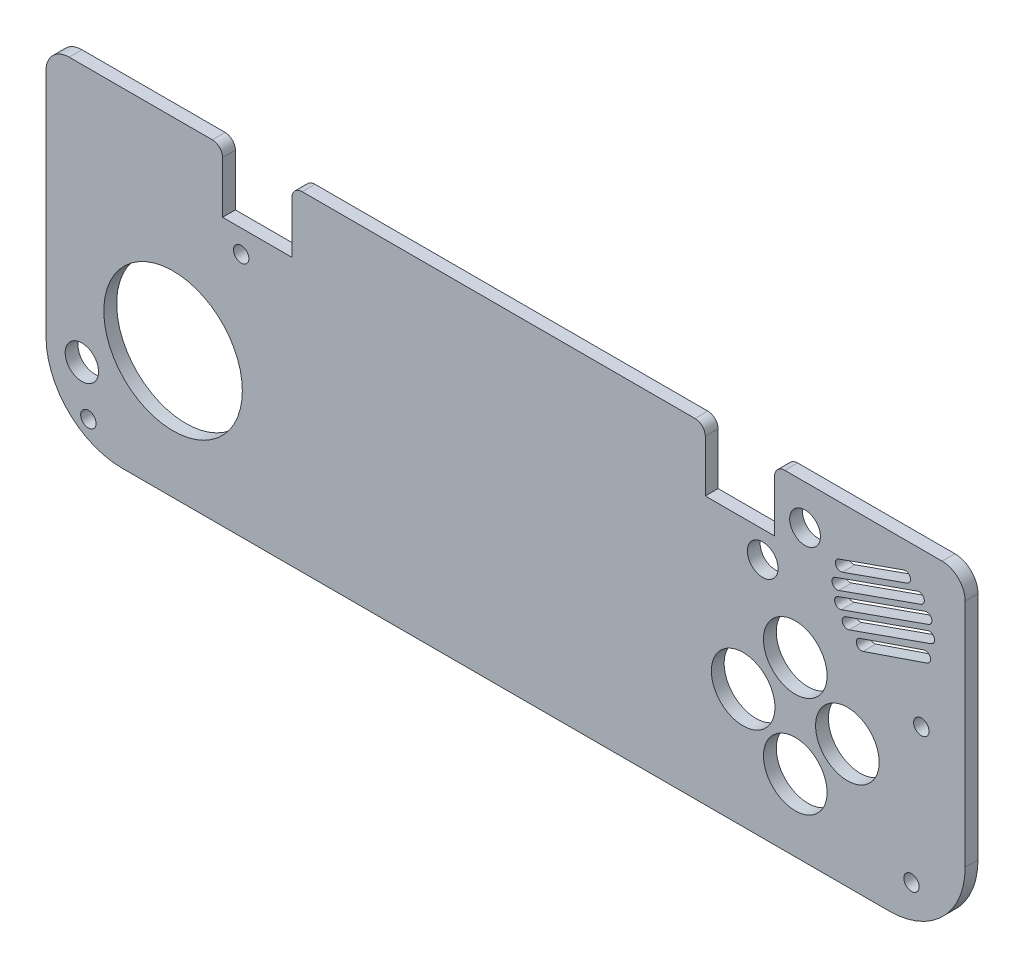
SolidWorks part; units mm, degrees
other "Caméra1"
ref_plane "Plan de face" through (0, 0, 0) normal (0, 0, 1) x (1, 0, 0)
ref_plane "Plan de dessus" through (0, 0, 0) normal (0, 1, 0) x (1, 0, 0)
ref_plane "Plan de droite" through (0, 0, 0) normal (1, 0, 0) x (0, 0, -1)
sketch "Esquisse20" plane through (0, 0, 0) normal (0, 0, 1) x (1, 0, 0)
  line L1 (14.8, -2) -> (164.37, -2)
  line L2 (0, 12.8) -> (0, 57.73)
  line L3 (4.5, 62.23) -> (174.67, 62.23)
  line L4 (179.17, 12.8) -> (179.17, 57.73)
  arc A0 (0, 57.73) -> (4.5, 62.23) centre (4.5, 57.73) cw
  arc A1 (174.67, 62.23) -> (179.17, 57.73) centre (174.67, 57.73) cw
  arc A2 (164.37, -2) -> (179.17, 12.8) centre (164.37, 12.8) ccw
  arc A3 (14.8, -2) -> (0, 12.8) centre (14.8, 12.8) cw
  point P7 (0, 62.23)
  point P10 (179.17, 62.23)
  point P14 (179.17, -2)
  point P17 (0, -2)
extrude "Boss.-Extru.1" add sketch "Esquisse20" along normal blind 2.5
sketch "Esquisse22" plane through (0, 0, 2.5) normal (0, 0, 1) x (1, 0, 0)
  line L0 (14.8, -2) -> (164.37, -2) construction
  line L1 (0, 57.73) -> (0, 12.8) construction
  circle A0 centre (24.77, 22.77) radius 13.5
  dimension "D1" = 24.77
  dimension "D2" = 24.77
extrude "Enlèv. mat.-Extru.1" cut sketch "Esquisse22" against normal blind 2.5
sketch "Esquisse23" plane through (0, 0, 2.5) normal (0, 0, 1) x (1, 0, 0)
  line L0 (14.8, -2) -> (164.37, -2) construction
  line L1 (0, 57.73) -> (0, 12.8) construction
  circle A0 centre (6.99, 11.97) radius 3.25
  circle A1 centre (-24.9782, 23.5691) radius 3.25
  dimension "D1" = 13.97
  dimension "D2" = 6.99
extrude "Enlèv. mat.-Extru.2" cut sketch "Esquisse23" against normal blind 2.5
sketch "Esquisse24" plane through (0, 0, 2.5) normal (0, 0, 1) x (1, 0, 0)
  line L0 (34.42, 58.87) -> (47.92, 50.15)
  line L1 (34.42, 58.87) -> (47.92, 58.87)
  line L2 (34.42, 58.87) -> (34.42, 50.15)
  line L3 (34.42, 50.15) -> (47.92, 50.15)
  line L4 (47.92, 58.87) -> (47.92, 50.15)
  line L5 (179.17, 12.8) -> (179.17, 57.73) construction
  line L7 (174.67, 62.23) -> (4.5, 62.23) construction
  point P4 (41.17, 54.51)
  dimension "D1" = 13.5
  dimension "D2" = 8.72
  dimension "D3" = 138
  dimension "D4" = 7.72
extrude "Enlèv. mat.-Extru.3" cut sketch "Esquisse24" against normal blind 2.5 contours L2 L3 L0 | L4 L1 L0 region at (43.42, 55.9633, 2.5) region at (38.92, 53.0567, 2.5)
sketch "Esquisse25" plane through (0, 0, 2.5) normal (0, 0, 1) x (1, 0, 0)
  line L0 (47.92, 58.87) -> (34.42, 58.87)
  line L1 (47.92, 58.87) -> (47.92, 62.2418)
  line L2 (34.42, 58.87) -> (34.42, 62.2418)
  line L3 (47.92, 62.2418) -> (34.42, 62.2418)
extrude "Enlèv. mat.-Extru.4" cut sketch "Esquisse25" against normal blind 2.5
fillet "Congé1" radius 2 2 edges at (47.92, 62.23, 1.25) (34.42, 62.23, 1.25)
sketch "Esquisse26" plane through (0, 0, 2.5) normal (0, 0, 1) x (1, 0, 0)
  line L0 (179.17, 12.8) -> (179.17, 57.73) construction
  line L1 (174.67, 62.23) -> (49.92, 62.23) construction
  circle A1 centre (156.21, 22.13) radius 6.2
  dimension "D2" = 22.96
  dimension "D3" = 40.1
sketch "Esquisse27" plane through (0, 0, 2.5) normal (0, 0, 1) x (1, 0, 0)
  line L0 (179.17, 12.8) -> (179.17, 57.73) construction
  line L1 (174.67, 62.23) -> (49.92, 62.23) construction
  circle A0 centre (146.05, 11.97) radius 6.2
  circle A1 centre (135.89, 21.23) radius 6.2
  circle A2 centre (146.05, 31.65) radius 6.2
  dimension "D1" = 33.12
  dimension "D2" = 43.28
  dimension "D3" = 33.12
  dimension "D4" = 30.58
  dimension "D5" = 41
  dimension "D6" = 50.26
extrude "Enlèv. mat.-Extru.5" cut sketch "Esquisse26" against normal blind 2.5
extrude "Enlèv. mat.-Extru.6" cut sketch "Esquisse27" against normal blind 2.5
sketch "Esquisse30" plane through (0, 0, 2.5) normal (0, 0, 1) x (1, 0, 0)
  line L0 (128.51, 58.87) -> (142.01, 50.15)
  line L1 (128.51, 58.87) -> (142.01, 58.87)
  line L2 (128.51, 58.87) -> (128.51, 50.15)
  line L3 (128.51, 50.15) -> (142.01, 50.15)
  line L4 (142.01, 58.87) -> (142.01, 50.15)
  line L5 (142.01, 58.87) -> (128.51, 50.15)
  line L6 (174.67, 62.23) -> (49.92, 62.23) construction
  line L7 (179.17, 12.8) -> (179.17, 57.73) construction
  line L8 (142.01, 58.87) -> (128.51, 58.87)
  line L9 (142.01, 58.87) -> (142.01, 62.2543)
  line L10 (128.51, 58.87) -> (128.51, 62.2543)
  line L11 (142.01, 62.2543) -> (128.51, 62.2543)
  point P4 (135.26, 54.51)
  line M7 (174.67, 62.23) -> (49.92, 62.23)
  dimension "D1" = 13.5
  dimension "D2" = 8.72
  dimension "D3" = 7.72
  dimension "D4" = 43.91
extrude "Enlèv. mat.-Extru.7" cut sketch "Esquisse30" against normal blind 2.5 contours L10 L1 L9 M7 | L5 L1 L0 | L5 L0 L2 | L0 L5 L3 | L4 L5 L0 region at (135.26, 57.4167, 2.5) region at (135.26, 60.55, 2.5) region at (130.76, 54.51, 2.5) region at (139.76, 54.51, 2.5) region at (135.26, 51.6033, 2.5)
fillet "Congé2" radius 2 2 edges at (142.01, 62.23, 1.25) (128.51, 62.23, 1.25)
sketch "Esquisse31" plane through (0, 0, 2.5) normal (0, 0, 1) x (1, 0, 0)
  line L0 (126.51, 62.23) -> (49.92, 62.23) construction
  line L1 (179.17, 12.8) -> (179.17, 57.73) construction
  circle A0 centre (147.96, 54.51) radius 3
  circle A1 centre (139.7, 44.99) radius 3
  dimension "D1" = 7.72
  dimension "D3" = 17.24
  dimension "D2" = 31.21
  dimension "D4" = 39.47
extrude "Enlèv. mat.-Extru.8" cut sketch "Esquisse31" against normal blind 2.5
sketch "Esquisse32" plane through (0, 0, 2.5) normal (0, 0, 1) x (1, 0, 0)
  line L0 (179.17, 12.8) -> (179.17, 57.73) construction
  line L1 (174.67, 62.23) -> (144.01, 62.23) construction
  line L2 (171.6853, 51.16) -> (154.7147, 45.16) construction
  line L3 (172.0186, 50.2172) -> (155.0481, 44.2172)
  line L4 (171.3519, 52.1028) -> (154.3814, 46.1028)
  line L5 (154.2, 48.16) -> (170.2, 53.8169) construction
  line L6 (153.8667, 49.1028) -> (169.8667, 54.7597)
  line L7 (154.5333, 47.2172) -> (170.5333, 52.874)
  line L8 (154.8754, 51.5808) -> (167.5246, 56.0529) construction
  line L9 (154.5421, 52.5236) -> (167.1912, 56.9957)
  line L10 (155.2088, 50.638) -> (167.8579, 55.1101)
  line L11 (156.2, 42.5031) -> (172.2, 48.16) construction
  line L12 (155.8667, 43.446) -> (171.8667, 49.1028)
  line L13 (156.5333, 41.5603) -> (172.5333, 47.2172)
  line L14 (158.9416, 40.2312) -> (171.4222, 44.5) construction
  line L17 (158.6179, 41.1774) -> (171.0986, 45.4462)
  line L18 (159.2652, 39.285) -> (171.7458, 43.5538)
  circle A0 centre (163.2, 48.16) radius 10
  circle A1 centre (163.2, 48.16) radius 9
  arc A2 (172.0186, 50.2172) -> (171.3519, 52.1028) centre (171.6853, 51.16) ccw
  arc A3 (154.3814, 46.1028) -> (155.0481, 44.2172) centre (154.7147, 45.16) ccw
  arc A4 (153.8667, 49.1028) -> (154.5333, 47.2172) centre (154.2, 48.16) ccw
  arc A5 (170.5333, 52.874) -> (169.8667, 54.7597) centre (170.2, 53.8169) ccw
  arc A6 (154.5421, 52.5236) -> (155.2088, 50.638) centre (154.8754, 51.5808) ccw
  arc A7 (167.8579, 55.1101) -> (167.1912, 56.9957) centre (167.5246, 56.0529) ccw
  arc A8 (155.8667, 43.446) -> (156.5333, 41.5603) centre (156.2, 42.5031) ccw
  arc A9 (172.5333, 47.2172) -> (171.8667, 49.1028) centre (172.2, 48.16) ccw
  arc A12 (158.6179, 41.1774) -> (159.2652, 39.285) centre (158.9416, 40.2312) ccw
  arc A13 (171.7458, 43.5538) -> (171.0986, 45.4462) centre (171.4222, 44.5) ccw
  point P9 (163.2, 48.16)
  point P16 (162.2, 50.9884)
  point P23 (161.2, 53.8169)
  point P30 (164.2, 45.3316)
  point P37 (165.1819, 42.3656)
  dimension "D1" = 15.97
  dimension "D3" = 0.589
  dimension "D2" = 14.07
  dimension "D4" = 3
  dimension "D5" = 3
  dimension "D6" = 3
extrude "Enlèv. mat.-Extru.9" cut sketch "Esquisse32" against normal blind 2.5 contours L10 A7 L9 A6 | L7 A5 L6 A4 | L3 A3 L4 A2 | L13 A9 L12 A8 | L18 A13 L17 A12
sketch "Esquisse33" plane through (0, 0, 2.5) normal (0, 0, 1) x (1, 0, 0)
  circle A0 centre (38.0467, 45.7343) radius 1.5
extrude "Enlèv. mat.-Extru.10" cut sketch "Esquisse33" against normal blind 10
sketch "Esquisse34" plane through (0, 0, 2.5) normal (0, 0, 1) x (1, 0, 0)
  line L0 (14.8, -2) -> (164.37, -2) construction
  line L1 (0, 57.73) -> (0, 12.8) construction
  circle A0 centre (8.26, 2.99) radius 1.5
  dimension "D1" = 4.99
  dimension "D2" = 8.26
extrude "Enlèv. mat.-Extru.11" cut sketch "Esquisse34" against normal blind 10
sketch "Esquisse35" plane through (0, 0, 2.5) normal (0, 0, 1) x (1, 0, 0)
  line L0 (14.8, -2) -> (164.37, -2) construction
  line L1 (179.17, 12.8) -> (179.17, 57.73) construction
  circle A0 centre (168.71, 5) radius 1.5
  dimension "D1" = 3
  dimension "D2" = 7
  dimension "D3" = 10.46
extrude "Enlèv. mat.-Extru.12" cut sketch "Esquisse35" against normal blind 10
sketch "Esquisse36" plane through (0, 0, 2.5) normal (0, 0, 1) x (1, 0, 0)
  line L0 (179.17, 12.8) -> (179.17, 57.73) construction
  line L1 (174.67, 62.23) -> (144.01, 62.23) construction
  circle A0 centre (170.62, 32.23) radius 1.5
  dimension "D1" = 8.55
  dimension "D2" = 30
extrude "Enlèv. mat.-Extru.13" cut sketch "Esquisse36" against normal blind 10
